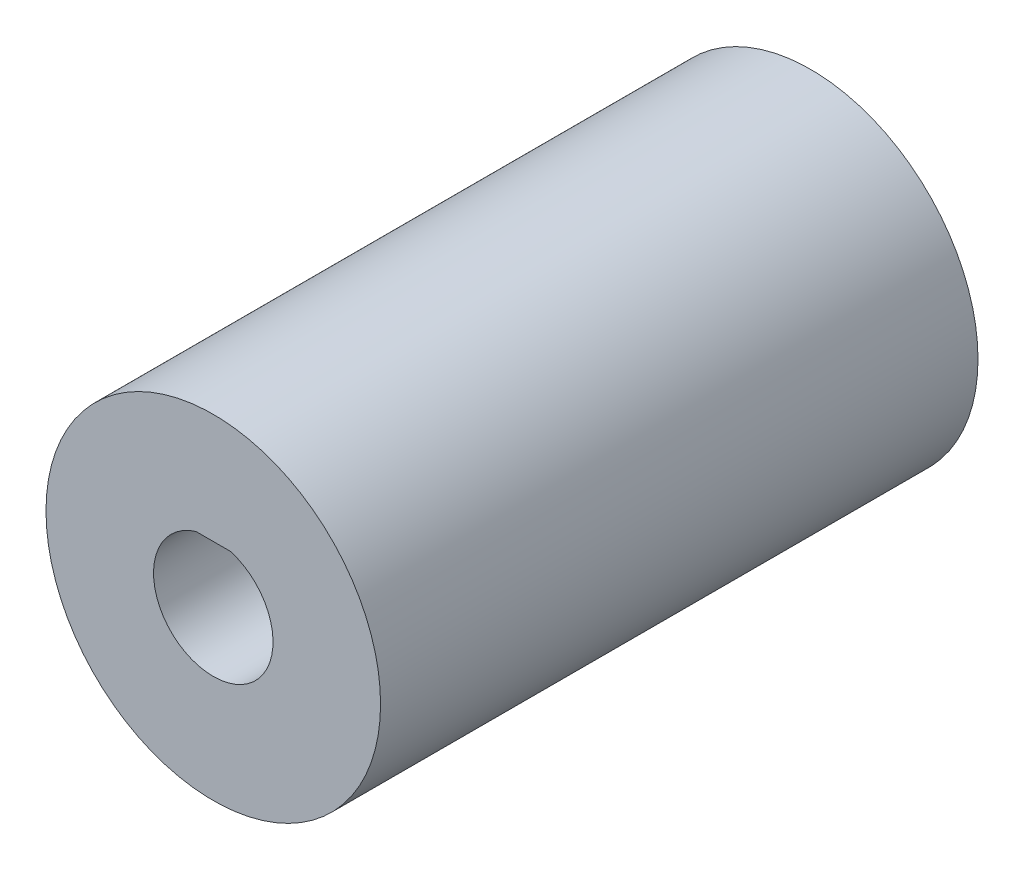
SolidWorks part; units mm, degrees
material "1060 Alloy"
ref_plane "Front Plane" through (0, 0, 0) normal (1, 0, 0) x (0, 1, 0)
ref_plane "Top Plane" through (0, 0, 0) normal (0, 0, 1) x (0, 1, 0)
ref_plane "Right Plane" through (0, 0, 0) normal (0, 1, 0) x (-1, 0, 0)
sketch "Sketch1" plane through (0, 0, 0) normal (0, 0, 1) x (0, 1, 0)
  circle A0 centre (0, 0) radius 7
  circle A1 centre (0, 0) radius 3
  dimension "D1" = 6
  dimension "D2" = 14
extrude "Boss-Extrude1" add sketch "Sketch1" along normal blind 25
sketch "Sketch2" plane through (0, 0, 25) normal (0, 0, 1) x (1, 0, 0)
  line L0 (-0.7283, 2.3916) -> (0.7283, 2.3916)
  arc A0 (-0.7283, 2.3916) -> (0.7283, 2.3916) centre (0, 0) ccw
  circle A1 centre (0, 0) radius 3 construction
  circle A2 centre (0, 0) radius 3
  dimension "D1" = 5
extrude "Boss-Extrude2" add sketch "Sketch2" against normal blind 10
